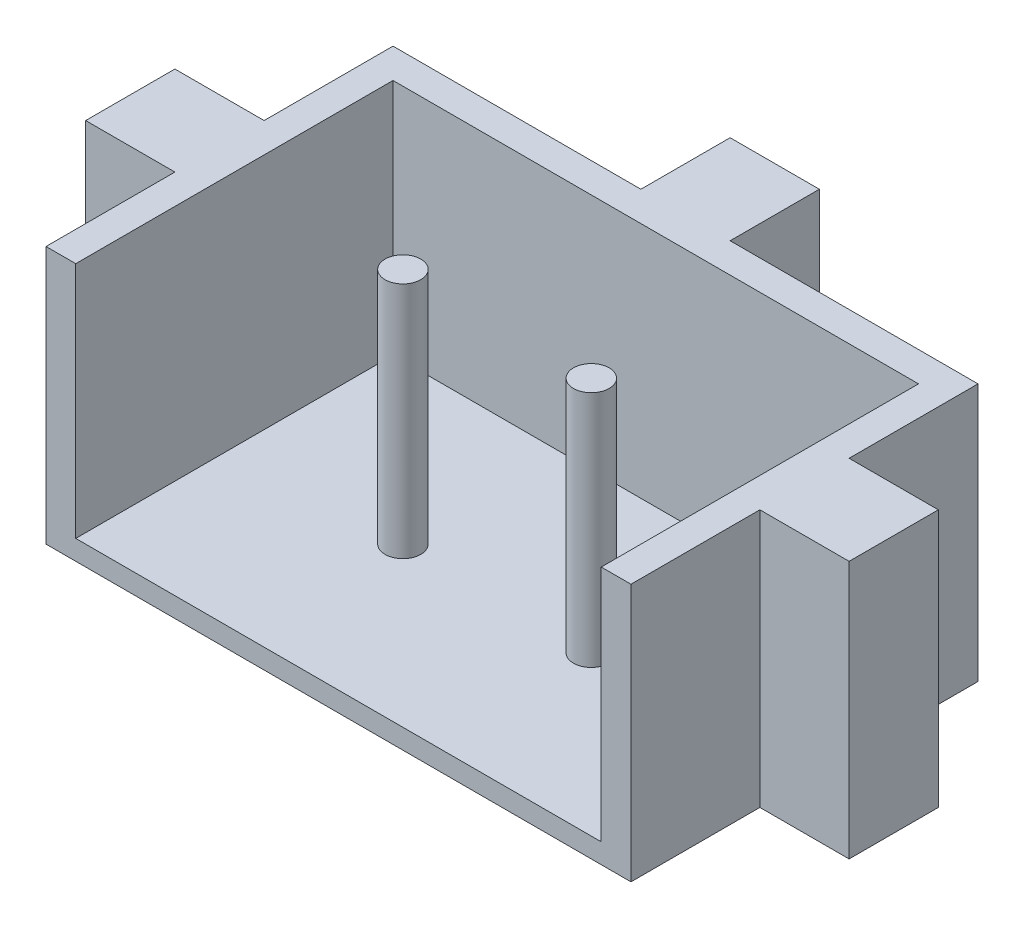
SolidWorks part; units mm, degrees
ref_plane "Alzado" through (0, 0, 0) normal (0, 0, 1) x (1, 0, 0)
ref_plane "Planta" through (0, 0, 0) normal (0, 1, 0) x (1, 0, 0)
ref_plane "Vista lateral" through (0, 0, 0) normal (1, 0, 0) x (0, 0, -1)
sketch "Croquis2" plane through (0, 0, 0) normal (0, 1, 0) x (1, 0, 0)
  line L0 (0, 10.287) -> (0, -10.6078) construction
  line L1 (14.75, -8.75) -> (-14.75, -8.75)
  line L2 (14.75, -8.75) -> (14.75, -2.25)
  line L3 (14.75, 8.75) -> (2.25, 8.75)
  line L4 (-14.75, -8.75) -> (-14.75, -2.25)
  line L5 (14.75, -8.75) -> (-14.75, 8.75) construction
  line L6 (14.75, 8.75) -> (-14.75, -8.75) construction
  line L7 (-10.7327, 0) -> (10.7937, 0) construction
  line L8 (19.25, -2.25) -> (14.75, -2.25)
  line L9 (2.25, 13.25) -> (-2.25, 13.25)
  line L10 (2.25, 13.25) -> (2.25, 8.75)
  line L12 (-2.25, 13.25) -> (-2.25, 8.75)
  line L13 (2.25, 13.25) -> (-2.25, 8.75) construction
  line L14 (2.25, 8.75) -> (-2.25, 13.25) construction
  line L15 (-19.25, 2.25) -> (-14.75, 2.25)
  line L16 (-19.25, 2.25) -> (-19.25, -2.25)
  line L17 (-19.25, -2.25) -> (-14.75, -2.25)
  line L19 (-19.25, 2.25) -> (-14.75, -2.25) construction
  line L20 (-19.25, -2.25) -> (-14.75, 2.25) construction
  line L22 (19.25, 2.25) -> (14.75, 2.25)
  line L23 (19.25, 2.25) -> (19.25, -2.25)
  line L32 (-2.25, 8.75) -> (-14.75, 8.75)
  line L33 (14.75, 2.25) -> (14.75, 8.75)
  line L34 (-14.75, 2.25) -> (-14.75, 8.75)
  point P0 (0, 0)
  point P10 (0, 11)
  point P15 (-17, 0)
  dimension "D1" = 4.5
  dimension "D2" = 4.5
  dimension "D3" = 4.5
  dimension "D4" = 4.5
  dimension "D5" = 29.5
  dimension "D6" = 17.5
extrude "Saliente-Extruir1" add sketch "Croquis2" along normal blind 13
sketch "Croquis4" plane through (0, 13, 0) normal (0, 1, 0) x (1, 0, 0)
  line L0 (-14.75, 8.75) -> (-14.75, -8.75) construction
  line L2 (-14.75, 8.75) -> (14.75, 8.75) construction
  line L3 (14.75, 8.75) -> (14.75, -8.75) construction
  line L4 (-13.25, -8.75) -> (-13.25, 7.25)
  line L5 (-14.75, -8.75) -> (14.75, -8.75) construction
  line L6 (-13.25, 7.25) -> (13.25, 7.25)
  line L7 (13.25, 7.25) -> (13.25, -8.75)
  line L8 (-13.25, -8.75) -> (13.25, -8.75)
  line L9 (0, 5.1469) -> (0, -6.906) construction
  circle A0 centre (4.75, -0.75) radius 0.9
  circle A1 centre (-4.75, -0.75) radius 0.9
  dimension "D4" = 1.8
  dimension "D5" = 8
  dimension "D6" = 4.75
  dimension "D1" = 1.5
  dimension "D2" = 1.5
  dimension "D3" = 1.5
extrude "Cortar-Extruir1" cut sketch "Croquis4" against normal offset from surface (12 mm away) 1 up to face at (0, 0, -2.75)
